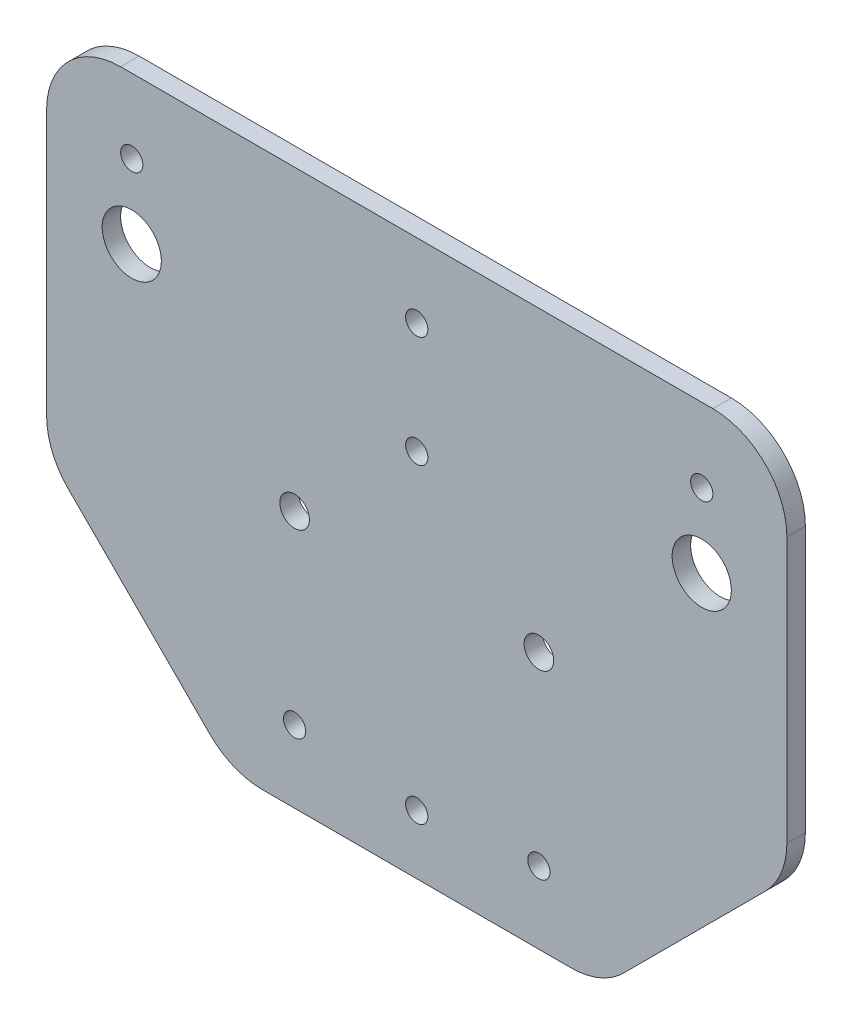
SolidWorks part; units mm, degrees
material "Maple"
ref_plane "Front Plane" through (0, 0, 0) normal (0, 0, 1) x (1, 0, 0)
ref_plane "Top Plane" through (0, 0, 0) normal (0, 1, 0) x (1, 0, 0)
ref_plane "Right Plane" through (0, 0, 0) normal (1, 0, 0) x (0, 0, -1)
sketch "Sketch1" plane through (0, 0, 0) normal (0, 0, 1) x (1, 0, 0)
  line L0 (50, 37.5) -> (-50, 37.5)
  line L1 (-50, -37.5) -> (50, -37.5) construction
  line L2 (-50, -37.5) -> (-50, 37.5) construction
  line L3 (-50, 37.5) -> (50, 37.5) construction
  line L4 (50, -37.5) -> (50, 37.5) construction
  line L5 (-50, -37.5) -> (50, 37.5) construction
  line L6 (-50, 37.5) -> (50, -37.5) construction
  line L7 (-50, 37.5) -> (-50, -12.5)
  line L8 (-50, -12.5) -> (-25, -37.5)
  line L9 (-25, -37.5) -> (25, -37.5)
  line L10 (0, 37.5) -> (0, -37.5) construction
  line L15 (-26.85, 7.5) -> (13.65, 7.5)
  line L16 (-26.85, 7.5) -> (-26.85, -13)
  line L17 (-26.85, -13) -> (13.65, -13)
  line L18 (13.65, 7.5) -> (13.65, -13)
  line L19 (50, -12.5) -> (25, -37.5)
  line L20 (50, 37.5) -> (50, -12.5)
  line L25 (-26.85, -2.75) -> (13.65, -2.75) construction
  line L26 (-6.6, 7.5) -> (-6.6, -13) construction
  circle A1 centre (0, -29.5) radius 1.5
  circle A2 centre (-16.5, -27.75) radius 1.5
  circle A3 centre (16.5, -27.75) radius 1.5
  circle A5 centre (-38.5, 17.5) radius 4
  circle A6 centre (38.5, 17.5) radius 4
  circle A7 centre (-29.5, 2.25) radius 1.5
  circle A8 centre (-29.5, -7.75) radius 1.5
  circle A9 centre (16.3, 2.25) radius 1.5
  circle A10 centre (16.3, -7.75) radius 1.5
  circle A11 centre (-16.5, -2.75) radius 2
  circle A12 centre (16.5, -2.75) radius 2
  circle A13 centre (38.5, 27.5) radius 1.5
  circle A14 centre (-38.5, 27.5) radius 1.5
  circle A15 centre (0, 12.5) radius 1.5
  circle A16 centre (0, 27.5) radius 1.5
  point P0 (0, 0)
  point P29 (-26.85, -2.75)
  dimension "D14" = 3
  dimension "D17" = 10
  dimension "D18" = 45.8
  dimension "D19" = 3
  dimension "D22" = 4
  dimension "D6" = 8
  dimension "D25" = 3
  dimension "D1" = 100
  dimension "D2" = 75
  dimension "D3" = 50
  dimension "D4" = 25
  dimension "D5" = 77
  dimension "D7" = 10
  dimension "D8" = 30
  dimension "D9" = 40.5
  dimension "D10" = 20.5
  dimension "D11" = 10.35
  dimension "D12" = 33
  dimension "D13" = 25
  dimension "D15" = 8
  dimension "D16" = 20
  dimension "D20" = 9.75
  dimension "D21" = 2
  dimension "D23" = 15
  dimension "D24" = 10
extrude "Boss-Extrude1" [suppressed] add sketch "Sketch1" along normal mid plane 2.5
fillet "Fillet1" [suppressed] radius 10
extrude "Boss-Extrude2" add sketch "Sketch1<3>" along normal mid plane 2.5 contours L20 L0 L7 L8 L9 L19 A3 A2 A1 L15 L18 L17 L16 A5 A6 | L18 L15 L16 L17 | A7 | A8 | A10 | A9 region at (48.75, 12.5, 0) region at (-6.4479, -2.75, 0)
sketch "Sketch1<3>" plane through (0, 0, 0) normal (0, 0, 1) x (1, 0, 0) same geometry as "Sketch1"
fillet "Fillet2" radius 10 6 edges at (50, -12.5, 0) (25, -37.5, 0) (-25, -37.5, 0) (-50, -12.5, 0) (-50, 37.5, 0) (50, 37.5, 0)
